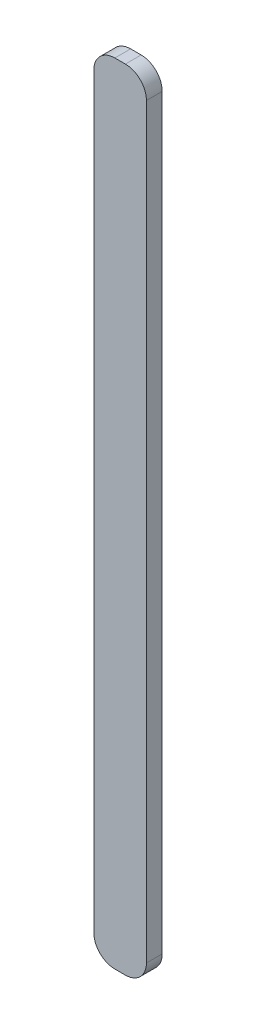
SolidWorks part; units mm, degrees
material "Beech"
ref_plane "Front" through (0, 0, 0) normal (0, 0, 1) x (1, 0, 0)
ref_plane "Top" through (0, 0, 0) normal (0, 1, 0) x (1, 0, 0)
ref_plane "Right" through (0, 0, 0) normal (1, 0, 0) x (0, 0, -1)
sketch "Sketch1" plane through (0, 0, 0) normal (0, 0, 1) x (1, 0, 0)
  line L1 (-5, -75) -> (5, -75)
  line L2 (-5, -75) -> (-5, 75)
  line L3 (-5, 75) -> (5, 75)
  line L4 (5, -75) -> (5, 75)
  line L5 (-5, -75) -> (5, 75) construction
  line L6 (-5, 75) -> (5, -75) construction
  point P0 (0, 0)
  dimension "D1" = 150
  dimension "D2" = 10
extrude "Boss-Extrude1" add sketch "Sketch1" along normal mid plane 3
fillet "Fillet1" radius 4 4 edges at (-5, -75, 0) (5, -75, 0) (-5, 75, 0) (5, 75, 0)
